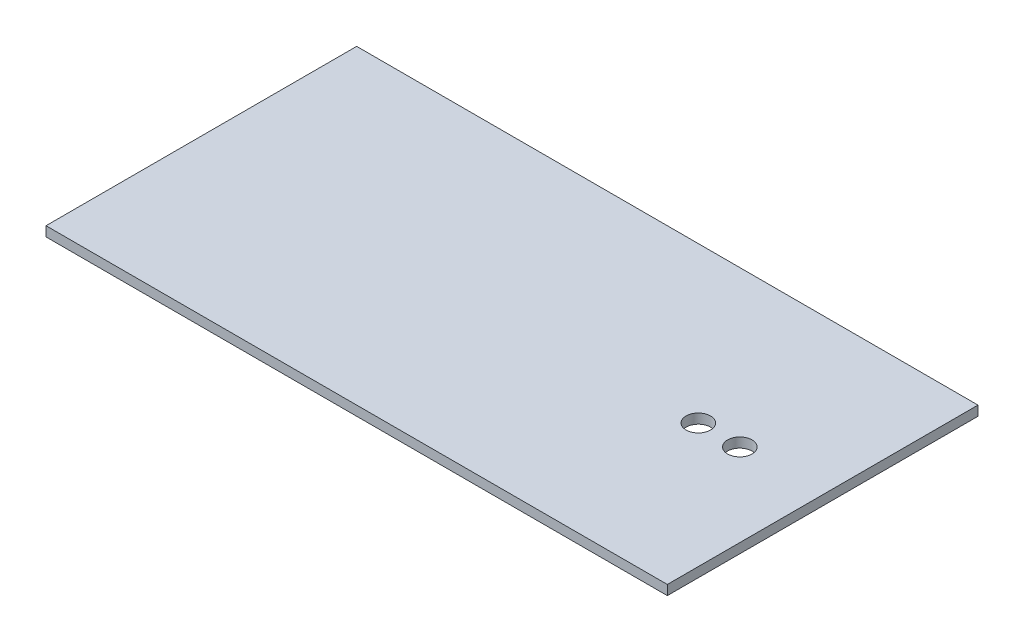
SolidWorks part; units mm, degrees
ref_plane "Front Plane" through (0, 0, 0) normal (0, 0, 1) x (1, 0, 0)
ref_plane "Top Plane" through (0, 0, 0) normal (0, 1, 0) x (1, 0, 0)
ref_plane "Right Plane" through (0, 0, 0) normal (1, 0, 0) x (0, 0, -1)
sketch "Sketch1" plane through (0, 0, 0) normal (0, 1, 0) x (1, 0, 0)
  line L1 (50.8, -25.4) -> (-50.8, -25.4)
  line L2 (50.8, -25.4) -> (50.8, 25.4)
  line L3 (50.8, 25.4) -> (-50.8, 25.4)
  line L4 (-50.8, -25.4) -> (-50.8, 25.4)
  line L5 (50.8, -25.4) -> (-50.8, 25.4) construction
  line L6 (50.8, 25.4) -> (-50.8, -25.4) construction
  point P0 (0, 0)
  dimension "D1" = 101.6
  dimension "D2" = 50.8
extrude "Boss-Extrude1" add sketch "Sketch1" along normal blind 1.5875
sketch "Sketch2" plane through (0, 1.5875, 0) normal (0, 1, 0) x (1, 0, 0)
  line L0 (-0.8731, 0) -> (0.8731, 0) construction
  circle A0 centre (37.2518, 0) radius 2
  circle A1 centre (30.47, 0) radius 2
  dimension "D1" = 4
  dimension "D2" = 4
  dimension "D3" = 6.7818
extrude "Cut-Extrude1" cut sketch "Sketch2" against normal through all
